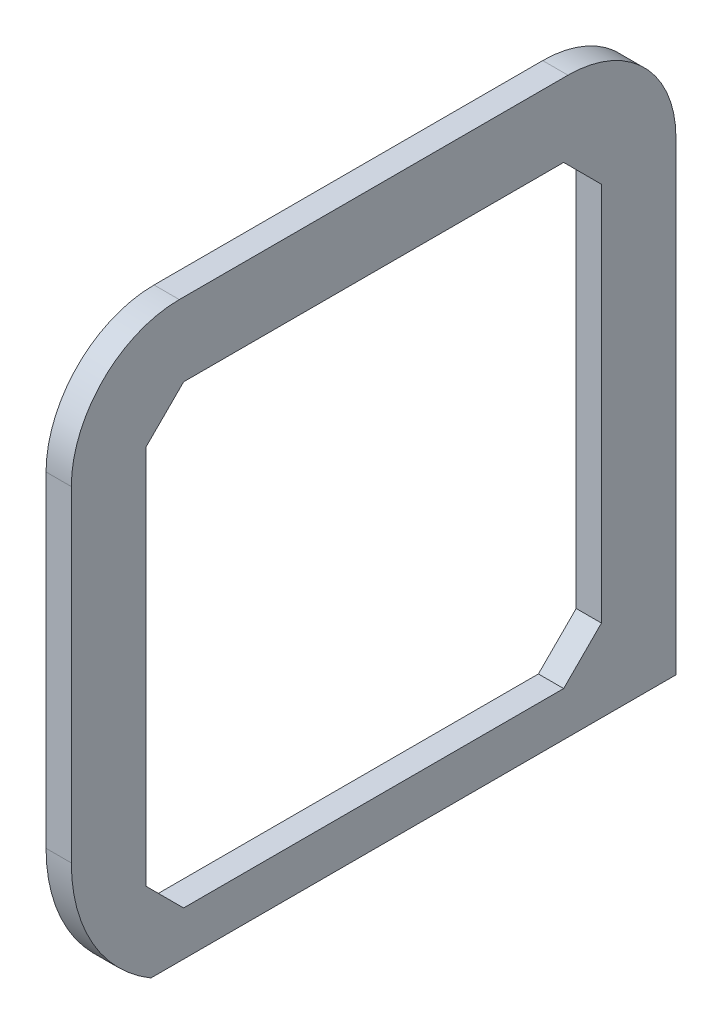
SolidWorks part; units mm, degrees
ref_plane "Front Plane" through (0, 0, 0) normal (0, 0, 1) x (1, 0, 0)
ref_plane "Top Plane" through (0, 0, 0) normal (0, 1, 0) x (1, 0, 0)
ref_plane "Right Plane" through (0, 0, 0) normal (1, 0, 0) x (0, 0, -1)
sketch "Sketch1" plane through (0, 0, 0) normal (0, 0, 1) x (1, 0, 0)
  line L0 (13.02, -7.9417) -> (17.7, -7.9417)
  line L1 (-10.5664, 13.02) -> (-10.5664, 70.02)
  line L2 (-10.5664, 70.02) -> (17.7, 70.02)
  line L3 (17.7, -7.9417) -> (17.7, 70.02)
  line L10 (12.7, -6.3331) -> (12.7, -7.9417) construction
  line L11 (13.02, -5.3171) -> (13.02, -4.2875)
  line L12 (11.651, -2.9185) -> (11.5392, -2.9185)
  line L13 (10.1702, -4.2875) -> (10.1702, -6.4021)
  line L14 (8.9631, -6.9029) -> (5.667, -3.6143)
  line L15 (4.8285, -1.5932) -> (4.8285, 1.5932)
  line L16 (5.667, 3.6143) -> (8.9631, 6.9029)
  line L17 (10.1702, 6.4021) -> (10.1702, 4.2875)
  line L18 (11.5392, 2.9185) -> (11.651, 2.9185)
  line L19 (13.02, 10.5773) -> (13.02, 4.2875)
  line L20 (6.3329, 13.02) -> (10.5626, 13.0198)
  line L22 (6.3329, 13.02) -> (4.2875, 13.02)
  line L23 (2.9185, 11.651) -> (2.9185, 11.5392)
  line L24 (4.2875, 10.1702) -> (6.4768, 10.1702)
  line L25 (6.981, 8.9509) -> (3.6723, 5.6497)
  line L26 (1.6558, 4.8158) -> (-1.6558, 4.8158)
  line L27 (-3.6723, 5.6497) -> (-6.981, 8.9509)
  line L28 (-6.4768, 10.1702) -> (-4.2875, 10.1702)
  line L29 (-2.9185, 11.5392) -> (-2.9185, 11.651)
  line L30 (-4.2875, 13.02) -> (-5.3171, 13.02)
  line L31 (-5.3171, 13.02) -> (-10.5664, 13.02)
  line L32 (13.02, -5.3171) -> (13.02, -7.9417)
  line L33 (13.02, -6.3331) -> (13.02, -7.9417) construction
  line L34 (13.02, 4.2875) -> (13.02, 5.3171) construction
  line L37 (5.3171, 13.02) -> (4.2875, 13.02) construction
  line L38 (-6.3331, 13.02) -> (-9.5504, 13.02) construction
  line L96 (12.7, -5.3171) -> (12.7, -4.2875) construction
  line L97 (11.651, -3.2385) -> (11.5392, -3.2385) construction
  line L98 (10.4902, -4.2875) -> (10.4902, -6.4021) construction
  line L99 (8.7371, -7.1294) -> (5.441, -3.8408) construction
  line L100 (4.5085, -1.5932) -> (4.5085, 1.5932) construction
  line L101 (5.441, 3.8408) -> (8.7371, 7.1294) construction
  line L102 (10.4902, 6.4021) -> (10.4902, 4.2875) construction
  line L103 (11.5392, 3.2385) -> (11.651, 3.2385) construction
  line L104 (12.7, 4.2875) -> (12.7, 5.3171) construction
  line L105 (12.7, 6.3331) -> (12.7, 9.5504) construction
  line L106 (9.5504, 12.7) -> (6.3331, 12.7) construction
  line L107 (5.3171, 12.7) -> (4.2875, 12.7) construction
  line L108 (3.2385, 11.651) -> (3.2385, 11.5392) construction
  line L109 (4.2875, 10.4902) -> (6.4768, 10.4902) construction
  line L110 (7.207, 8.7244) -> (3.8983, 5.4232) construction
  line L111 (1.6558, 4.4958) -> (-1.6558, 4.4958) construction
  line L112 (-3.8983, 5.4232) -> (-7.207, 8.7244) construction
  line L113 (-6.4768, 10.4902) -> (-4.2875, 10.4902) construction
  line L114 (-3.2385, 11.5392) -> (-3.2385, 11.651) construction
  line L115 (-4.2875, 12.7) -> (-5.3171, 12.7) construction
  line L116 (-6.3331, 12.7) -> (-9.5504, 12.7) construction
  arc A0 (13.02, -4.2875) -> (11.651, -2.9185) centre (11.651, -4.2875) ccw
  arc A1 (11.5392, -2.9185) -> (10.1702, -4.2875) centre (11.5392, -4.2875) ccw
  arc A2 (8.9631, -6.9029) -> (10.1702, -6.4021) centre (9.4628, -6.4021) ccw
  arc A3 (4.8285, -1.5932) -> (5.667, -3.6143) centre (7.6835, -1.5932) ccw
  arc A4 (5.667, 3.6143) -> (4.8285, 1.5932) centre (7.6835, 1.5932) ccw
  arc A5 (10.1702, 6.4021) -> (8.9631, 6.9029) centre (9.4628, 6.4021) ccw
  arc A6 (10.1702, 4.2875) -> (11.5392, 2.9185) centre (11.5392, 4.2875) ccw
  arc A7 (11.651, 2.9185) -> (13.02, 4.2875) centre (11.651, 4.2875) ccw
  arc A8 (4.2875, 13.02) -> (2.9185, 11.651) centre (4.2875, 11.651) ccw
  arc A9 (2.9185, 11.5392) -> (4.2875, 10.1702) centre (4.2875, 11.5392) ccw
  arc A10 (6.981, 8.9509) -> (6.4768, 10.1702) centre (6.4768, 9.4563) ccw
  arc A11 (1.6558, 4.8158) -> (3.6723, 5.6497) centre (1.6558, 7.6708) ccw
  arc A12 (-3.6723, 5.6497) -> (-1.6558, 4.8158) centre (-1.6558, 7.6708) ccw
  arc A13 (-6.4768, 10.1702) -> (-6.981, 8.9509) centre (-6.4768, 9.4563) ccw
  arc A14 (-4.2875, 10.1702) -> (-2.9185, 11.5392) centre (-4.2875, 11.5392) ccw
  arc A15 (-2.9185, 11.651) -> (-4.2875, 13.02) centre (-4.2875, 11.651) ccw
  arc A16 (13.02, 10.5773) -> (10.5626, 13.0198) centre (10.5918, 10.5918) ccw
  arc A17 (13.0198, 10.5625) -> (10.5626, 13.0198) centre (10.5918, 10.5918) ccw construction
  arc A114 (12.7, -5.3171) -> (12.7, -6.3331) centre (12.7, -5.8251) ccw construction
  arc A115 (12.7, -4.2875) -> (11.651, -3.2385) centre (11.651, -4.2875) ccw construction
  arc A116 (11.5392, -3.2385) -> (10.4902, -4.2875) centre (11.5392, -4.2875) ccw construction
  arc A117 (8.7371, -7.1294) -> (10.4902, -6.4021) centre (9.4628, -6.4021) ccw construction
  arc A118 (4.5085, -1.5932) -> (5.441, -3.8408) centre (7.6835, -1.5932) ccw construction
  arc A119 (5.441, 3.8408) -> (4.5085, 1.5932) centre (7.6835, 1.5932) ccw construction
  arc A120 (10.4902, 6.4021) -> (8.7371, 7.1294) centre (9.4628, 6.4021) ccw construction
  arc A121 (10.4902, 4.2875) -> (11.5392, 3.2385) centre (11.5392, 4.2875) ccw construction
  arc A122 (11.651, 3.2385) -> (12.7, 4.2875) centre (11.651, 4.2875) ccw construction
  arc A123 (12.7, 6.3331) -> (12.7, 5.3171) centre (12.7, 5.8251) ccw construction
  arc A124 (12.6998, 10.5664) -> (12.7, 9.5504) centre (12.7, 10.0584) ccw construction
  arc A125 (12.6998, 10.5664) -> (10.5664, 12.6998) centre (10.5918, 10.5918) ccw construction
  arc A126 (9.5504, 12.7) -> (10.5664, 12.6998) centre (10.0584, 12.7) ccw construction
  arc A127 (5.3171, 12.7) -> (6.3331, 12.7) centre (5.8251, 12.7) ccw construction
  arc A128 (4.2875, 12.7) -> (3.2385, 11.651) centre (4.2875, 11.651) ccw construction
  arc A129 (3.2385, 11.5392) -> (4.2875, 10.4902) centre (4.2875, 11.5392) ccw construction
  arc A130 (7.207, 8.7244) -> (6.4768, 10.4902) centre (6.4768, 9.4563) ccw construction
  arc A131 (1.6558, 4.4958) -> (3.8983, 5.4232) centre (1.6558, 7.6708) ccw construction
  arc A132 (-3.8983, 5.4232) -> (-1.6558, 4.4958) centre (-1.6558, 7.6708) ccw construction
  arc A133 (-6.4768, 10.4902) -> (-7.207, 8.7244) centre (-6.4768, 9.4563) ccw construction
  arc A134 (-4.2875, 10.4902) -> (-3.2385, 11.5392) centre (-4.2875, 11.5392) ccw construction
  arc A135 (-3.2385, 11.651) -> (-4.2875, 12.7) centre (-4.2875, 11.651) ccw construction
  arc A136 (-6.3331, 12.7) -> (-5.3171, 12.7) centre (-5.8251, 12.7) ccw construction
  arc A137 (-10.5664, 12.6998) -> (-9.5504, 12.7) centre (-10.0584, 12.7) ccw construction
  dimension "D1" = 57
  dimension "D6" = 5
  dimension "D8" = 0.32
  dimension "D7" = 6.2898
  dimension "D9" = 4.2297
extrude "Boss-Extrude1" add sketch "Sketch1" along normal blind 56 contours L3 L2 L1 L31 L30 A15 L29 A14 L28 A13 L27 A12 L26 A11 L25 A10 L24 A9 L23 A8 L22 L20 A16 L19 A7 L18 A6 L17 A5 L16 A4 L15 A3 L14 A2 L13 A1 L12 A0 L11 L32 L0
sketch "Sketch14" plane through (17.7, 0, 0) normal (1, 0, 0) x (0, 0, -1)
  line L4 (-56, -7.9417) -> (-56, 70.02) construction
  line L5 (0, -7.9417) -> (0, 70.02) construction
  line L6 (-56, 70.02) -> (0, 70.02) construction
  line L11 (0, 21.02) -> (-56, 21.02) construction
  line L12 (-28, 70.02) -> (-28, 21.02) construction
  line L14 (-49.1, 21.02) -> (-6.9, 21.02)
  line L15 (-49.1, 21.02) -> (-49.1, 63.22)
  line L16 (-49.1, 63.22) -> (-6.9, 63.22)
  line L17 (-6.9, 21.02) -> (-6.9, 63.22)
  point P14 (-28, 63.22)
  dimension "D1" = 42.2
  dimension "D2" = 42.2
other "AlignGroup1"
extrude "Cut-Extrude1" cut sketch "Sketch14" against normal blind 56
chamfer "Chamfer1" distance 3.5 4 edges at (3.5668, 21.02, 6.9) (3.5668, 21.02, 49.1) (3.5668, 63.22, 6.9) (3.5668, 63.22, 49.1)
fillet "Fillet1" radius 10 2 edges at (3.5668, 70.02, 56) (3.5668, 70.02, 0)
sketch "Sketch16" plane through (17.7, 0, 0) normal (1, 0, 0) x (0, 0, -1)
  line L1 (-56, -7.9417) -> (-43.6, -7.9417)
  line L2 (-56, -7.9417) -> (-56, 15.0583)
  line L3 (-56, 15.0583) -> (-43.6, 15.0583)
  line L4 (-43.6, -7.9417) -> (-43.6, 15.0583)
  dimension "D1" = 23
  dimension "D2" = 12.4
extrude "Cut-Extrude3" cut sketch "Sketch16" against normal through all
sketch "Sketch17" plane through (0, 0, 56) normal (0, 0, 1) x (1, 0, 0)
  line L0 (17.7, 42.12) -> (-10.5664, 42.12) construction
  line L2 (-13.62, 51.12) -> (1.8336, 51.12)
  line L3 (-13.62, 51.12) -> (-13.62, 33.12)
  line L4 (17.7, 24.52) -> (17.7, 59.72)
  line L5 (-10.5664, 24.52) -> (17.7, 24.52)
  line L6 (-10.5664, 59.72) -> (-10.5664, 24.52)
  line L7 (17.7, 59.72) -> (-10.5664, 59.72)
  line L8 (17.7, 24.52) -> (17.7, 59.72) construction
  line L9 (-10.5664, 24.52) -> (17.7, 24.52) construction
  line L10 (-10.5664, 59.72) -> (-10.5664, 24.52) construction
  line L11 (17.7, 59.72) -> (-10.5664, 59.72) construction
  line L12 (-13.62, 33.12) -> (1.8336, 33.12)
  line L13 (1.8336, 51.12) -> (1.8336, 33.12)
  point P10 (1.8336, 42.12)
  dimension "D2" = 18
  dimension "D3" = 12.4
  dimension "D1" = 0
extrude "Cut-Extrude4" cut sketch "Sketch17" against normal up to next
fillet "Fillet4" radius 15 1 edges at (3.5668, 15.0583, 56)
sketch "Sketch18" plane through (0, 0, 0) normal (0, 0, -1) x (-1, 0, 0)
  line L0 (-15.3597, 16.9143) -> (-37.3681, 16.9143)
  line L1 (-15.3597, 72.8358) -> (14.0825, 72.8358)
  line L2 (-15.3597, 72.8358) -> (-15.3597, 16.9143)
  line L3 (-15.3597, -12.2016) -> (14.0825, -12.2016)
  line L4 (14.0825, 72.8358) -> (14.0825, -12.2016)
  line L5 (-37.3681, 16.9143) -> (-37.3681, -12.2016)
  line L6 (-37.3681, -12.2016) -> (-15.3597, -12.2016)
  dimension "D1" = 85.0374
  dimension "D2" = 29.4422
extrude "Cut-Extrude5" cut sketch "Sketch18" against normal through all
